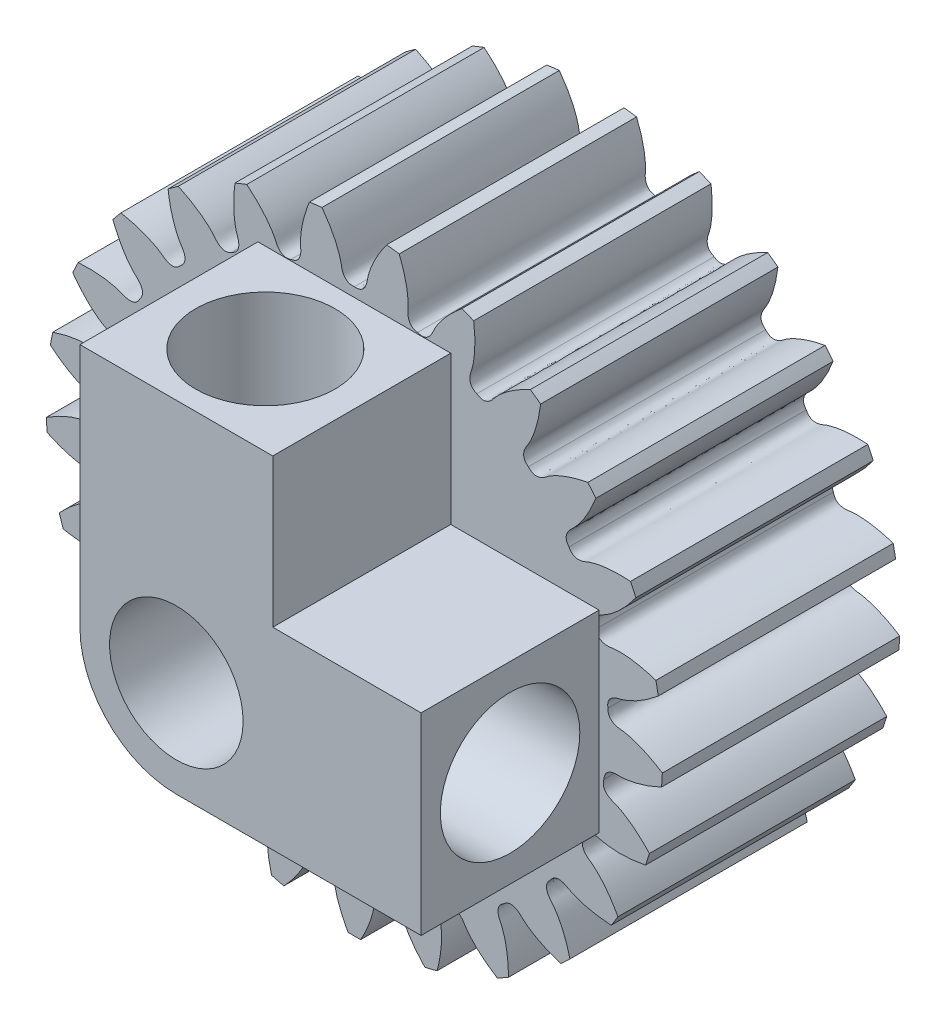
SolidWorks part; units mm, degrees
material "PLA Black"
ref_plane "Front" through (0, 0, 0) normal (0, 0, 1) x (1, 0, 0)
ref_plane "Top" through (0, 0, 0) normal (0, 1, 0) x (1, 0, 0)
ref_plane "Right" through (0, 0, 0) normal (1, 0, 0) x (0, 0, -1)
ref_axis "Axis1" through (0, 0, -15.6032) along (0, 0, 1)
sketch "Gear-BaseSketch" plane through (0, 0, 0) normal (0, 0, 1) x (1, 0, 0)
  circle A0 centre (0, 0) radius 10.3909
  dimension "D1" = 20.7818
extrude "33.0 Diametral Pitch, 20.78mm P.D." add sketch "Gear-BaseSketch" along normal mid plane 8
sketch "Tooth-Sketch; Backlash: 0.0000mm" plane through (0, 0, 0) normal (0, 0, 1) x (1, 0, 0)
  line L0 (0, 0) -> (0, 10.3909) construction
  arc A0 (-1.0905, 10.334) -> (1.0905, 10.334) centre (0, -0.094) cw
  circle A1 centre (0, 0) radius 10.3909 construction
  spline S0 degree 3 poles (-1.0905, 10.334) (-1.0138, 10.2299) (-0.9082, 10.0753) (-0.7851, 9.8689) (-0.7088, 9.729) (-0.6442, 9.5985) (-0.5903, 9.4783) (-0.5464, 9.369) (-0.5115, 9.2711) (-0.4845, 9.1851) (-0.4645, 9.1115) (-0.4506, 9.0507) (-0.4416, 9.0039) (-0.4365, 8.9698) (-0.432, 8.9444) (-0.4246, 8.9083) (-0.4122, 8.8596) (-0.3912, 8.7995) (-0.3638, 8.742) (-0.3272, 8.686) (-0.2761, 8.6321) (-0.1724, 8.5642) (-0.0681, 8.5594) (0, 8.5647) knots 0 0 0 0 0.176711 0.2556 0.328177 0.394444 0.454399 0.508044 0.555377 0.596399 0.63111 0.65951 0.681599 0.696189 0.706616 0.716848 0.746535 0.775185 0.80367 0.83335 0.866218 0.904587 1 1 1 1
  spline S1 degree 3 poles (1.0905, 10.334) (1.0138, 10.2299) (0.9082, 10.0753) (0.7851, 9.8689) (0.7088, 9.729) (0.6442, 9.5985) (0.5903, 9.4783) (0.5464, 9.369) (0.5115, 9.2711) (0.4845, 9.1851) (0.4645, 9.1115) (0.4506, 9.0507) (0.4416, 9.0039) (0.4365, 8.9698) (0.432, 8.9444) (0.4246, 8.9083) (0.4122, 8.8596) (0.3912, 8.7995) (0.3638, 8.742) (0.3272, 8.686) (0.2761, 8.6321) (0.1724, 8.5642) (0.0681, 8.5594) (0, 8.5647) knots 0 0 0 0 0.176711 0.2556 0.328177 0.394444 0.454399 0.508044 0.555377 0.596399 0.63111 0.65951 0.681599 0.696189 0.706616 0.716848 0.746535 0.775185 0.80367 0.83335 0.866218 0.904587 1 1 1 1
extrude "Tooth-Cut, Fine Pitch Involute 20 deg" cut sketch "Tooth-Sketch; Backlash: 0.0000mm" against normal through all and the other way through all
pattern_circular "Tooth Pattern, 25 / 25" count 25 over 360 about axis through (0, 0, -15.6032) along (0, 0, 1) of "Tooth-Cut, Fine Pitch Involute 20 deg"
sketch "Sketch4" plane through (0, 0, 4) normal (0, 0, 1) x (1, 0, 0)
  circle A0 centre (0, 0) radius 2.25
  dimension "D1" = 4.5
extrude "Cut-Extrude2" cut sketch "Sketch4" against normal through all contours A0
sketch "Sketch6" plane through (0, 0, 4) normal (0, 0, 1) x (1, 0, 0)
  circle A0 centre (0, 0) radius 3.25
  circle A1 centre (0, 0) radius 2.25
  circle A2 centre (0, 0) radius 2.25 construction
  dimension "D1" = 6.5
extrude "Boss-Extrude2" add sketch "Sketch6" along normal blind 6
sketch "Sketch9" plane through (0, 0, 4) normal (0, 0, 1) x (1, 0, 0)
  line L0 (-3.25, 0) -> (-3.25, 8.25)
  line L1 (-3.25, 8.25) -> (3.25, 8.25)
  line L2 (3.25, 8.25) -> (3.25, 3.25)
  line L3 (3.25, 3.25) -> (8.25, 3.25)
  line L4 (8.25, 3.25) -> (8.25, -3.25)
  line L5 (8.25, -3.25) -> (0, -3.25)
  circle A0 centre (0, 0) radius 3.25 construction
  circle A1 centre (0, 0) radius 3.25 construction
  arc A2 (-3.25, 0) -> (0, -3.25) centre (0, 0) cw
  dimension "D1" = 5
extrude "Boss-Extrude4" add sketch "Sketch9" along normal through all
ref_plane "Plane1" through (0, 3.25, 0) normal (0, 1, 0) x (1, 0, 0)
sketch "Sketch10" plane through (0, 8.25, 0) normal (0, 1, 0) x (1, 0, 0)
  line L0 (-3.25, -7) -> (3.25, -7) construction
  line L1 (-3.25, -10) -> (-3.25, -4) construction
  line L2 (3.25, -10) -> (3.25, -4) construction
  line L3 (0, -4) -> (0, -10) construction
  line L4 (3.25, -10) -> (-3.25, -10) construction
  circle A0 centre (0, -7) radius 2.35
  dimension "D1" = 4.7
extrude "Cut-Extrude3" cut sketch "Sketch10" against normal blind 8
sketch "Sketch11" plane through (8.25, 0, 0) normal (1, 0, 0) x (0, 0, -1)
  line L0 (-7, 3.25) -> (-7, -3.25) construction
  line L1 (-10, 3.25) -> (-4, 3.25) construction
  line L2 (-10, -3.25) -> (-4, -3.25) construction
  line L3 (-10, 0) -> (-4, -0.4033) construction
  line L4 (-10, -3.25) -> (-10, 3.25) construction
  line L7 (-4, -3.25) -> (-4, 2.4434) construction
  circle A0 centre (-7, 0) radius 2.35
  dimension "D1" = 4.7
extrude "Cut-Extrude4" cut sketch "Sketch11" against normal blind 8 contours A0
